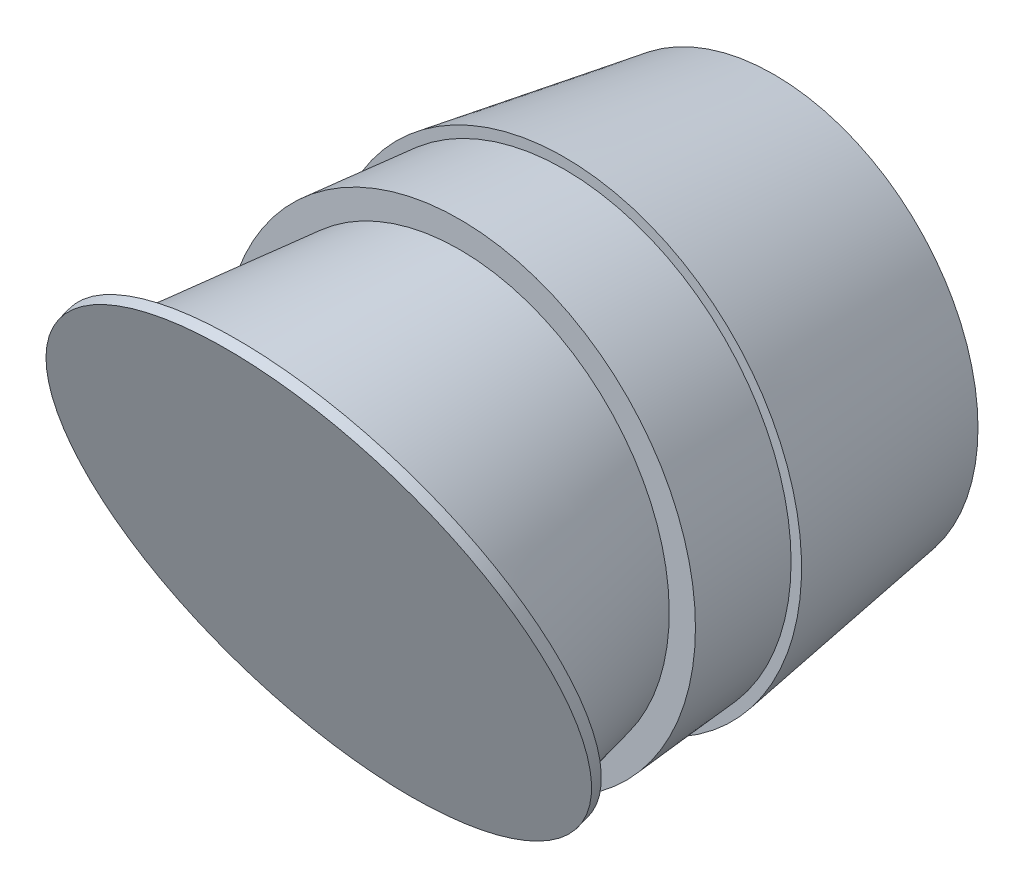
SolidWorks part; units mm, degrees
ref_plane "Front Plane" through (0, 0, 0) normal (0, 0, 1) x (1, 0, 0)
ref_plane "Top Plane" through (0, 0, 0) normal (0, 1, 0) x (1, 0, 0)
ref_plane "Right Plane" through (0, 0, 0) normal (1, 0, 0) x (0, 0, -1)
sketch "Sketch1" plane through (0, 0, 0) normal (0, 0, 1) x (1, 0, 0)
  line L0 (0, 34.9907) -> (0, -37.6588) construction
  line L1 (-13.89, -17.5) -> (14.3357, -17.5) construction
  circle A0 centre (0, 0) radius 10
  circle A1 centre (0, 0) radius 11.25
  point P8 (0, 10)
  dimension "D1" = 20
  dimension "D3" = 22.5
  dimension "D2" = 17.5
sketch "Sketch2" plane through (0, 0, 0) normal (1, 0, 0) x (0, 0, -1)
  line L0 (-19.9862, 0) -> (11.8569, 0) construction
ref_plane "Plane1" through (0, -2.2475, 5.8549) normal (0, -0.3584, 0.9336) x (1, 0, 0)
sketch "Sketch3" plane through (0, -2.2475, 5.8549) normal (0, -0.3584, 0.9336) x (1, 0, 0)
  line L2 (0, 19.9432) -> (0, -19.0864) construction
  circle A0 centre (0, 2.4074) radius 11.25
  circle A1 centre (0, 2.4074) radius 12.25
  point P4 (0, 13.6574)
  dimension "D1" = 22.5
  dimension "D2" = 1
extrude "Boss-Extrude1" add sketch "Sketch1" against normal blind 5 draft 5 contours A1
sketch "Sketch4" plane through (0, 0, -5) normal (0, 0, -1) x (-1, 0, 0)
  circle A1 centre (0, 0) radius 10.8126 construction
  circle A3 centre (0, 0) radius 10.8126 construction
  circle A4 centre (0, 0) radius 11.3126
  dimension "D1" = 0.5
extrude "Boss-Extrude2" add sketch "Sketch4" along normal blind 10 draft 9
loft "Loft2" add section "Sketch3" section "Sketch1<38>" connector at (-0.0206, 10.5028, 10.7493) connector at (0.0303, 10, 0)
sketch "Sketch1<38>" plane through (0, 0, 0) normal (0, 0, 1) x (1, 0, 0) same geometry as "Sketch1"
extrude "Boss-Extrude4" add sketch "Sketch3<7>" against normal blind 0.5 contours A1
sketch "Sketch3<7>" plane through (0, -2.2475, 5.8549) normal (0, -0.3584, 0.9336) x (1, 0, 0) same geometry as "Sketch3"
